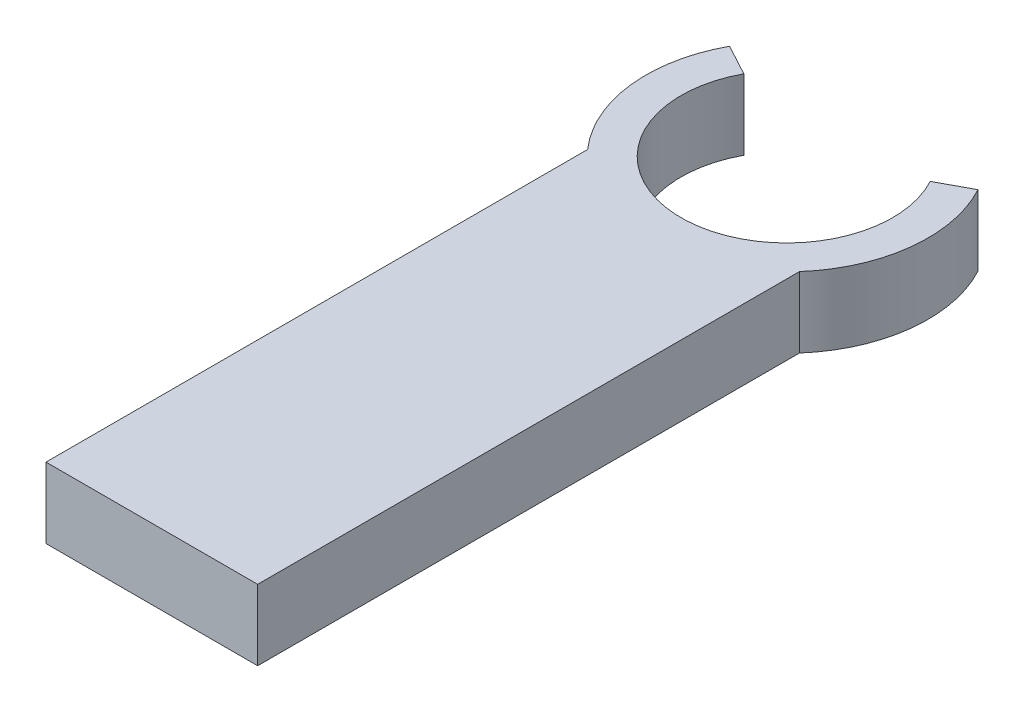
SolidWorks part; units mm, degrees
ref_plane "Front Plane" through (0, 0, 0) normal (0, 0, 1) x (1, 0, 0)
ref_plane "Top Plane" through (0, 0, 0) normal (0, 1, 0) x (1, 0, 0)
ref_plane "Right Plane" through (0, 0, 0) normal (1, 0, 0) x (0, 0, -1)
sketch "Sketch1" plane through (0, 0, 0) normal (0, 1, 0) x (1, 0, 0)
  line L1 (-15, 0) -> (-14.9891, 0)
  line L2 (15, 0) -> (15.0109, 0)
  line L4 (-15, -90) -> (15, -90) construction
  line L5 (-15, -90) -> (15, -90)
  line L6 (-15, -90) -> (-14.9907, -13.2393)
  line L7 (15, -90) -> (15.0093, -13.2182)
  line L8 (15, 0) -> (15.0109, 0)
  line L9 (-13.2052, 7.1149) -> (-17.607, 9.4865)
  line L10 (13.2052, 7.1149) -> (17.607, 9.4865)
  line L11 (-14.9892, -0.5702) -> (-14.9891, 0)
  arc A0 (-13.2052, 7.1149) -> (13.2052, 7.1149) centre (0, 0) ccw
  arc A1 (-17.607, 9.4865) -> (-14.9907, -13.2393) centre (0, 0) ccw
  arc A2 (15.0093, -13.2182) -> (17.607, 9.4865) centre (0, 0) ccw
  point P12 (0, -90)
  dimension "D1" = 30
  dimension "D2" = 40
  dimension "D4" = 30
extrude "Boss-Extrude1" add sketch "Sketch1" along normal blind 10 contours L6 A1 L9 A0 L10 A2 L7 L5
